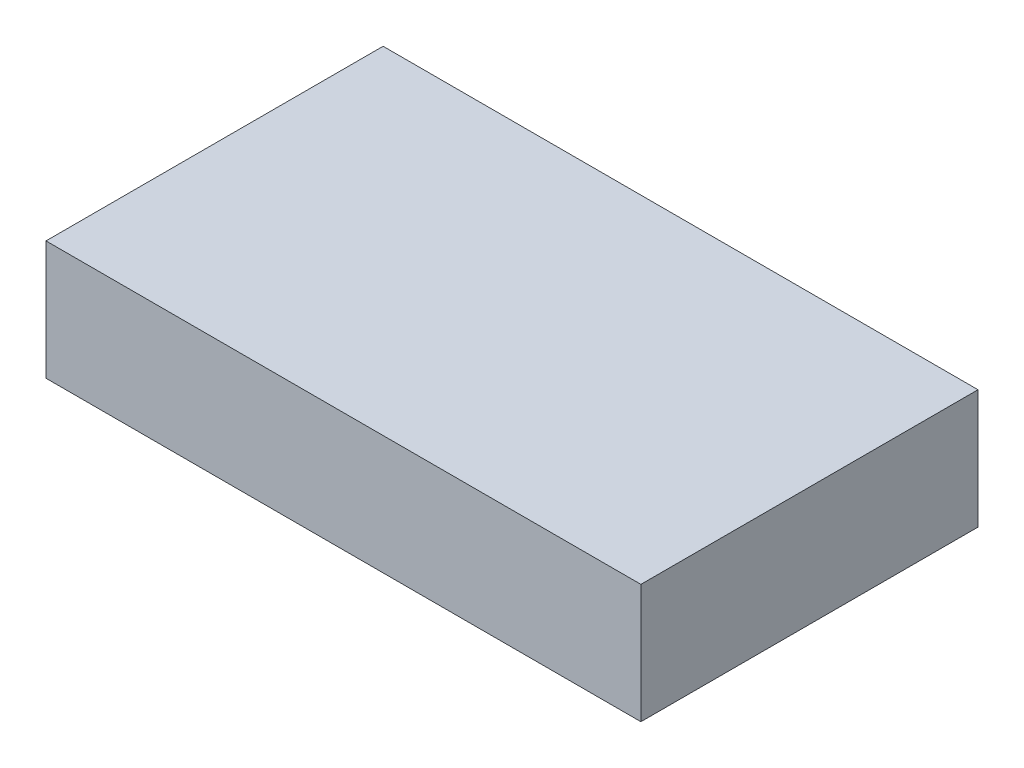
SolidWorks part; units mm, degrees
material "Maple"
ref_plane "Front Plane" through (0, 0, 0) normal (0, 0, 1) x (1, 0, 0)
ref_plane "Top Plane" through (0, 0, 0) normal (0, 1, 0) x (1, 0, 0)
ref_plane "Right Plane" through (0, 0, 0) normal (1, 0, 0) x (0, 0, -1)
sketch "Sketch1" plane through (0, 0, 0) normal (0, 1, 0) x (1, 0, 0)
  line L1 (0, 0) -> (30, 0)
  line L2 (0, 0) -> (0, 17)
  line L3 (0, 17) -> (30, 17)
  line L4 (30, 0) -> (30, 17)
  dimension "D1" = 30
  dimension "D2" = 17
extrude "Boss-Extrude1" add sketch "Sketch1" along normal blind 6
ref_plane "Plane1" through (0, 3, 0) normal (0, 1, 0) x (1, 0, 0)
